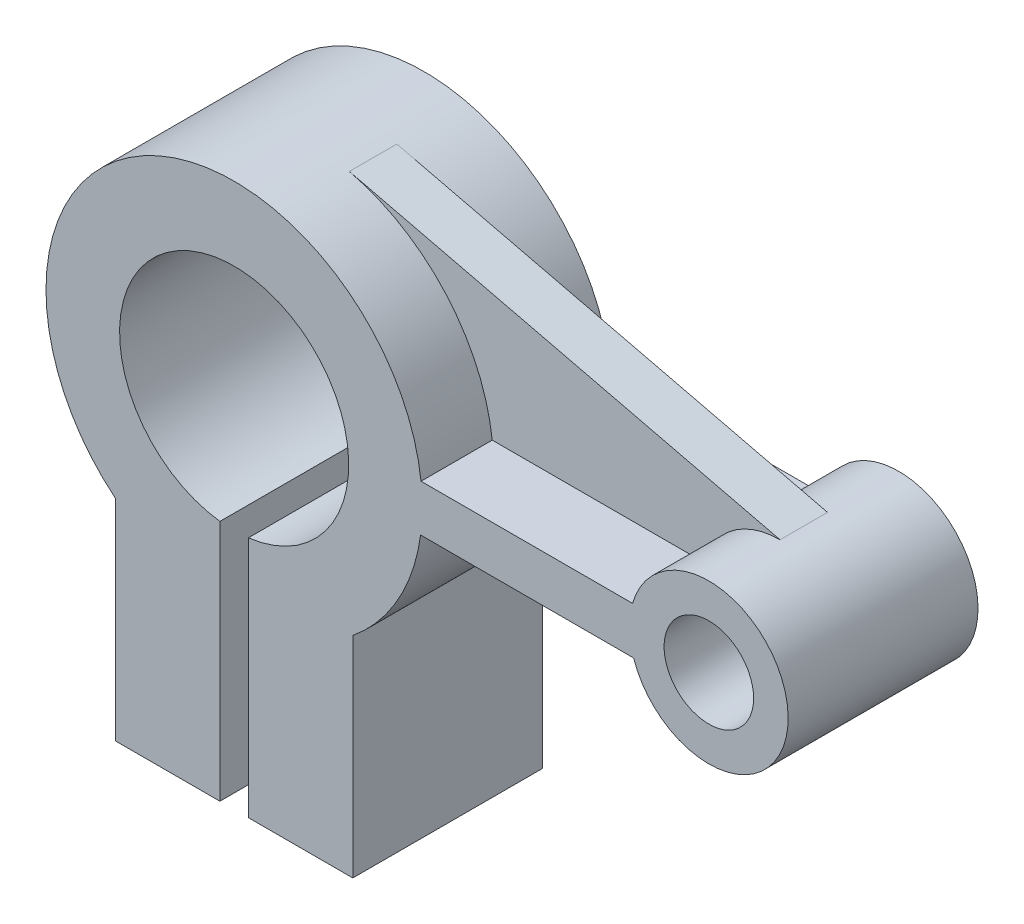
SolidWorks part; units mm, degrees
ref_plane "Front Plane" through (0, 0, 0) normal (0, 0, 1) x (1, 0, 0)
ref_plane "Top Plane" through (0, 0, 0) normal (0, 1, 0) x (1, 0, 0)
ref_plane "Right Plane" through (0, 0, 0) normal (1, 0, 0) x (0, 0, -1)
sketch "Sketch2" plane through (0, 0, 0) normal (0, 0, 1) x (1, 0, 0)
  line L0 (-126.8132, 5.2896) -> (48.9284, 5.2896) construction
  line L1 (-87.1827, 58.376) -> (-87.1827, -63.5376) construction
  line L2 (-47.8155, 9.8501) -> (-3.2486, 9.8501)
  line L3 (-3.0236, 0) -> (-47.9068, 0)
  line L4 (-90.1827, -18.6578) -> (-90.1827, -69.7104)
  line L5 (-84.1827, -18.6578) -> (-84.1827, -69.7104)
  line L6 (-112.1827, -69.7104) -> (-112.1827, -25.4606)
  line L7 (-62.1827, -69.7104) -> (-84.1827, -69.7104)
  line L8 (-62.1827, -69.7104) -> (-62.1827, -25.4606)
  line L9 (-112.1827, -69.7104) -> (-90.1827, -69.7104)
  arc A0 (-84.1827, -18.6578) -> (-90.1827, -18.6578) centre (-87.1827, 5.2896) ccw
  arc A2 (-3.0236, 0) -> (-3.2486, 9.8501) centre (12.8173, 5.2896) ccw
  circle A3 centre (12.8173, 5.2896) radius 9.4276
  arc A4 (-62.1827, -25.4606) -> (-47.9068, 0) centre (-87.1827, 5.2896) ccw
  arc A5 (-47.8155, 9.8501) -> (-112.1827, -25.4606) centre (-87.1827, 5.2896) ccw
  dimension "D1" = 100
  dimension "D2" = 75
  dimension "D3" = 75
extrude "Boss-Extrude1" add sketch "Sketch2" along normal mid plane 40 contours A5 L6 L9 L4 A0 L5 L7 L8 A4 L3 A2 L2
extrude "Cut-Extrude1" cut sketch "Sketch2<3>" against normal mid plane 40 contours A3
sketch "Sketch2<3>" plane through (0, 0, 0) normal (0, 0, 1) x (1, 0, 0) same geometry as "Sketch2"
sketch "Sketch4" plane through (0, 0, 0) normal (0, 0, 1) x (1, 0, 0)
  line L0 (-77.9119, 43.8205) -> (12.8173, 21.9903)
  arc A0 (-47.8155, 9.8501) -> (-112.1827, -25.4606) centre (-87.1827, 5.2896) ccw construction
  arc A1 (-3.0236, 0) -> (-3.2486, 9.8501) centre (12.8173, 5.2896) ccw construction
rib "Rib14" sketch "Sketch4" sketch "Sketch4" thickness 10 extrusion direction parallel to sketch draft on no parameters "D1"=10
